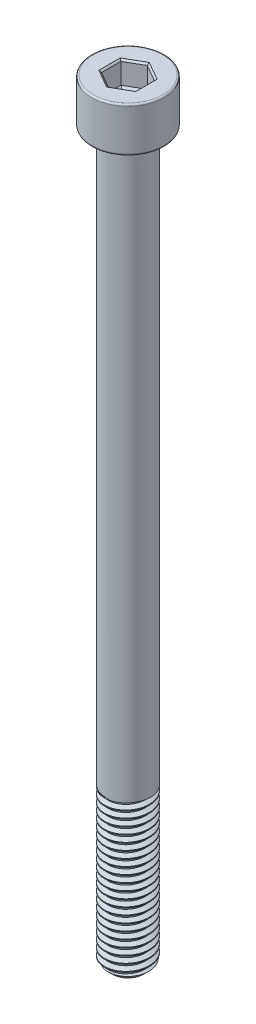
SolidWorks part; units mm, degrees
material "AISI Type A2 Tool Steel"
ref_plane "Front Plane" through (0, 0, 0) normal (0, 0, 1) x (1, 0, 0)
ref_plane "Top Plane" through (0, 0, 0) normal (0, 1, 0) x (1, 0, 0)
ref_plane "Right Plane" through (0, 0, 0) normal (1, 0, 0) x (0, 0, -1)
sketch "Sketch1" plane through (0, 0, 0) normal (0, 1, 0) x (1, 0, 0)
  circle A0 centre (0, 0) radius 4
  dimension "D1" = 8
extrude "Boss-Extrude1" add sketch "Sketch1" along normal blind 28
thread "Thread1" pitch 1.25 method cut profile "Thread Profile1" start angle 0, offset 2, length 0, pitch 1.25, diameter 8
ref_plane "Plane1" through (-4, 30, 0) normal (0, 0, 1) x (-1, 0, 0)
sketch "Thread Profile1" plane through (-4, 30, 0) normal (0, 0, 1) x (-1, 0, 0)
  line L0 (0, 0) -> (0, 1.25) construction
  line L11 (0, 0) -> (0, 1.0937)
  line L12 (0, 1.0937) -> (-0.6766, 0.7031)
  line L13 (-0.6766, 0.7031) -> (-0.6766, 0.3906)
  line L15 (-0.6766, 0.3906) -> (0, 0)
  line L17 (-0.6766, 0.5469) -> (0, 0.5469) construction
  point P2 (0, 0)
  dimension "Pitch" = 1.25
  dimension "Profile_Angle" = 60
  dimension "Profile_Land" = 0.3125
  dimension "Profile_Height" = 0.6766
sketch "Sketch2" plane through (0, 28, 0) normal (0, 1, 0) x (1, 0, 0)
  circle A0 centre (0, 0) radius 4
  dimension "D1" = 8
extrude "Boss-Extrude2" add sketch "Sketch2" along normal blind 102
sketch "Sketch5" plane through (0, 130, 0) normal (0, 1, 0) x (1, 0, 0)
  circle A0 centre (0, 0) radius 6.5
  dimension "D1" = 13
extrude "Boss-Extrude3" add sketch "Sketch5" along normal blind 8
sketch "Sketch6" plane through (0, 0, 0) normal (0, 0, 1) x (1, 0, 0)
  line L0 (0, 0) -> (0, 0.7245) construction
  line L1 (0, 0) -> (4.01, 0) construction
  line L2 (4.01, 0) -> (4.01, 1.2)
  line L3 (4.01, 1.2) -> (2.81, 0)
  line L4 (2.81, 0) -> (4.01, 0)
  dimension "D1" = 1.2
  dimension "D2" = 45
  dimension "D3" = 4.01
revolve "Cut-Revolve1" cut sketch "Sketch6" angle 360 about L0
fillet "Fillet1" radius 0.3 2 edges at (0, 130, 6.5) (0, 138, 6.5)
sketch "Sketch7" plane through (0, 138, 0) normal (0, 1, 0) x (1, 0, 0)
  line L1 (0, 3.4641) -> (-3, 1.7321)
  line L2 (-3, 1.7321) -> (-3, -1.7321)
  line L3 (-3, -1.7321) -> (0, -3.4641)
  line L4 (0, -3.4641) -> (3, -1.7321)
  line L5 (3, -1.7321) -> (3, 1.7321)
  line L6 (3, 1.7321) -> (0, 3.4641)
  circle A0 centre (0, 0) radius 3 construction
  dimension "D1" = 6
extrude "Cut-Extrude1" cut sketch "Sketch7" against normal blind 4
chamfer "Chamfer1" distance 0.3 angle 45 6 edges at (-3, 138, 0) (-1.5, 138, 2.5981) (1.5, 138, 2.5981) (3, 138, 0) (1.5, 138, -2.5981) (-1.5, 138, -2.5981)
sketch "Sketch8" plane through (0, 134, 0) normal (0, 1, 0) x (1, 0, 0)
  line L1 (0, 3.4641) -> (-3, 1.7321)
  line L2 (-3, 1.7321) -> (-3, -1.7321)
  line L3 (-3, -1.7321) -> (0, -3.4641)
  line L4 (0, -3.4641) -> (3, -1.7321)
  line L5 (3, -1.7321) -> (3, 1.7321)
  line L6 (3, 1.7321) -> (0, 3.4641)
  circle A0 centre (0, 0) radius 3 construction
extrude "Cut-Extrude2" cut sketch "Sketch8" against normal blind 0.4 draft 60
